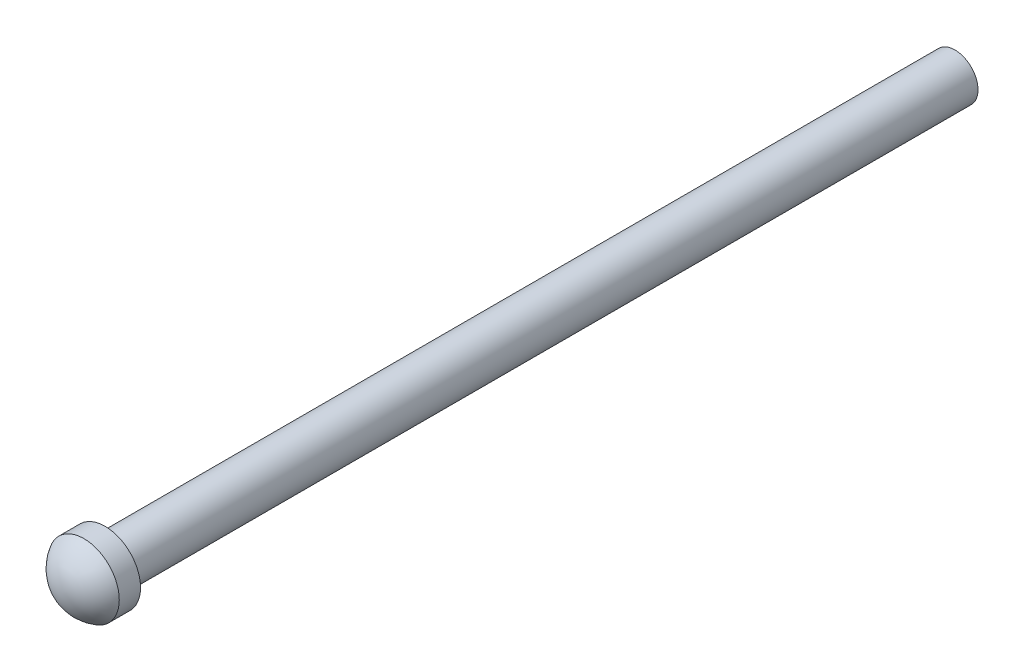
SolidWorks part; units mm, degrees
ref_plane "Front Plane" through (0, 0, 0) normal (0, 0, 1) x (1, 0, 0)
ref_plane "Top Plane" through (0, 0, 0) normal (0, 1, 0) x (1, 0, 0)
ref_plane "Right Plane" through (0, 0, 0) normal (1, 0, 0) x (0, 0, -1)
sketch "Sketch1" plane through (0, 0, 0) normal (0, 0, 1) x (1, 0, 0)
  circle A2 centre (5, 60) radius 3.25
  circle A3 centre (5, 60) radius 3.25
  dimension "D1" = 0.25
sketch "Sketch2" plane through (5, 0, 0) normal (1, 0, 0) x (0, 0, -1)
  line L0 (0, 0) -> (120, 0) construction
  line L1 (0, 0) -> (120, 0)
sweep "Sweep1" add profiles "Sketch1" path "Sketch2"
sketch "Sketch3" plane through (0, 0, 0) normal (0, 0, 1) x (1, 0, 0)
  circle A0 centre (5, 60) radius 5
extrude "Boss-Extrude1" add sketch "Sketch3" along normal blind 3
dome "Dome1" faces to dome 1 distance 3 reverse direction no elliptical dome no face at (10, 60, 3) parameters "D1"=3
